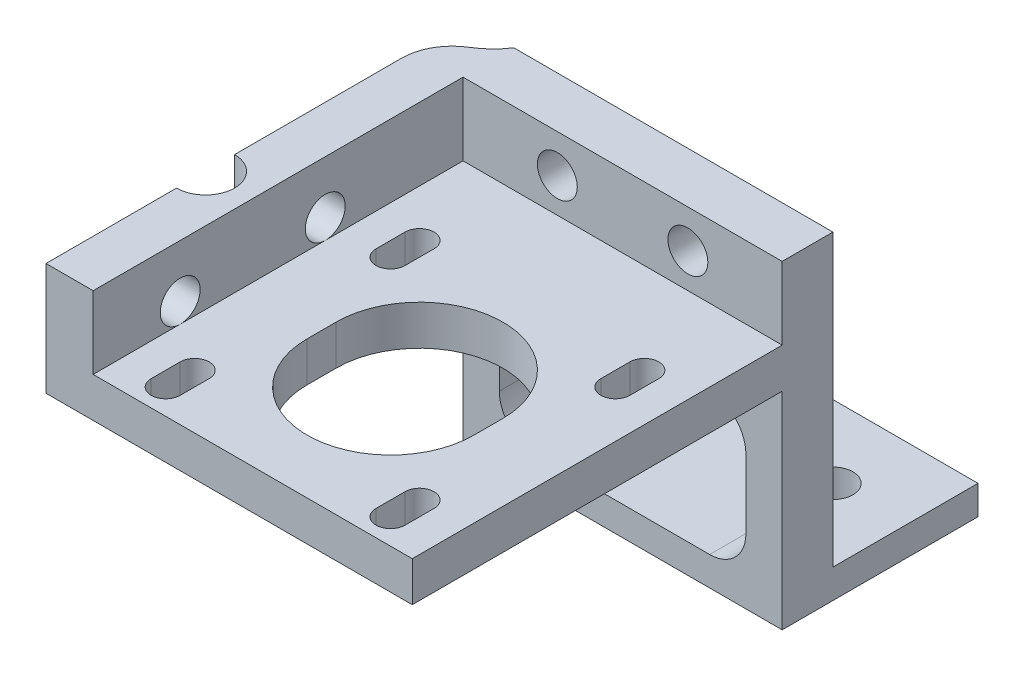
SolidWorks part; units mm, degrees
ref_plane "Front Plane" through (0, 0, 0) normal (0, 0, 1) x (1, 0, 0)
ref_plane "Top Plane" through (0, 0, 0) normal (0, 1, 0) x (1, 0, 0)
ref_plane "Right Plane" through (0, 0, 0) normal (1, 0, 0) x (0, 0, -1)
sketch "Sketch1" plane through (0, 0, 0) normal (1, 0, 0) x (0, 0, -1)
  line L0 (0, 0) -> (0, -62)
  line L1 (0, -62) -> (-5, -62)
  line L3 (-5, 0) -> (0, 0)
  line L4 (-56, 2.5) -> (-65, 2.5)
  line L5 (-65, 2.5) -> (-65, -15.5)
  arc A0 (-5, 0) -> (-56, 2.5) centre (-28.7567, 36.813) cw
  arc A1 (-5, -62) -> (-65, -15.5) centre (-67.324, -80.4584) ccw
  dimension "D3" = 51
  dimension "D5" = 43.813
  dimension "D8" = 65
  dimension "D1" = 5
  dimension "D2" = 62
  dimension "D4" = 2.5
  dimension "D6" = 9
  dimension "D7" = 18
  dimension "D9" = 5
extrude "Boss-Extrude1" add sketch "Sketch1" along normal blind 42 and the other way blind 42
sketch "Sketch2" plane through (0, 0, 0) normal (0, 0, -1) x (-1, 0, 0)
  line L0 (42, -62) -> (-42, -62) construction
  line L1 (-12, -54) -> (12, -54)
  line L2 (-17, -49) -> (-17, -25.5)
  line L3 (-12, -20.5) -> (12, -20.5)
  line L4 (17, -49) -> (17, -25.5)
  line L5 (42, -62) -> (42, 0) construction
  line L6 (42, 0) -> (-42, 0) construction
  line L7 (-42, -62) -> (-42, 0) construction
  line L8 (42, 2.5) -> (-42, 2.5) construction
  line L9 (-42, 0) -> (-27, 0)
  line L10 (-42, 0) -> (-42, 2.5)
  line L11 (-42, 2.5) -> (-27, 2.5)
  line L12 (-27, 0) -> (-27, 2.5)
  line L14 (42, 0) -> (27, 0)
  line L15 (42, 0) -> (42, 2.5)
  line L16 (42, 2.5) -> (27, 2.5)
  line L17 (27, 0) -> (27, 2.5)
  circle A0 centre (-36, -6) radius 2.75
  circle A1 centre (36, -6) radius 2.75
  circle A2 centre (36, -56) radius 2.75
  circle A3 centre (-36, -56) radius 2.75
  arc A4 (12, -20.5) -> (17, -25.5) centre (12, -25.5) cw
  arc A5 (12, -54) -> (17, -49) centre (12, -49) ccw
  arc A6 (-12, -54) -> (-17, -49) centre (-12, -49) cw
  arc A7 (-17, -25.5) -> (-12, -20.5) centre (-12, -25.5) cw
  arc A8 (-42, -8.3208) -> (-42, -53.6792) centre (-65.2788, -31) cw
  arc A9 (42, -8.3208) -> (42, -53.6792) centre (65.2788, -31) ccw
  line M7 (42, 0) -> (-42, 0)
  line M8 (-42, 0) -> (-42, -62)
  line M10 (42, -62) -> (42, 0)
  dimension "D1" = 5.5
  dimension "D2" = 5.5
  dimension "D3" = 5.5
  dimension "D4" = 5.5
  dimension "D9" = 5
  dimension "D18" = 8.3208
  dimension "D20" = 32.5
  dimension "D21" = 8.3208
  dimension "D23" = 32.5
  dimension "D5" = 33.5
  dimension "D6" = 34
  dimension "D7" = 8
  dimension "D8" = 25
  dimension "D10" = 6
  dimension "D11" = 6
  dimension "D12" = 6
  dimension "D13" = 6
  dimension "D14" = 6
  dimension "D15" = 6
  dimension "D16" = 6
  dimension "D17" = 6
  dimension "D19" = 8.3208
  dimension "D22" = 8.3208
  dimension "D24" = 15
  dimension "D25" = 15
extrude "Cut-Extrude1" cut sketch "Sketch2" against normal through all contours A0 | A8 M8 | A7 L2 A6 L1 A5 L4 A4 L3 | A3 | A2 | A1 | L17 L15 L16 M7 | L12 L11 L10 M7 | A9 M10 region at (0, -37.25, 0) region at (34.5, 1.25, 0) region at (-38.2626, -31, 0) region at (-34.5, 1.25, 0) region at (38.2626, -31, 0) region at (36, -6, 0) region at (-36, -6, 0) region at (-36, -56, 0) region at (36, -56, 0)
sketch "Sketch3" plane through (0, -62, 0) normal (0, -1, 0) x (-1, 0, 0)
  line L0 (42, -5) -> (27, -5)
  line L1 (42, -5) -> (-42, -5) construction
  line L2 (27, -5) -> (27, -65)
  line L3 (36.7131, -65) -> (-36.7131, -65) construction
  line L4 (0, -33) -> (0, -37) construction
  line L5 (-27, -65) -> (-27, -5)
  line L6 (-27, -5) -> (-42, -5)
  line L7 (-42, -5) -> (-42, -65)
  line L8 (-42, -65) -> (-27, -65)
  line L9 (42, -65) -> (42, -5)
  line L10 (42, -65) -> (27, -65)
  line L11 (11.5, -33) -> (11.5, -37)
  line L12 (-11.5, -33) -> (-11.5, -37)
  line L13 (15.5, -48.5) -> (15.5, -52.5) construction
  line L14 (17.5, -48.5) -> (17.5, -52.5)
  line L15 (13.5, -48.5) -> (13.5, -52.5)
  line L16 (15.5, -17.5) -> (15.5, -21.5) construction
  line L17 (17.5, -17.5) -> (17.5, -21.5)
  line L18 (13.5, -17.5) -> (13.5, -21.5)
  line L19 (42, 0) -> (-42, 0) construction
  line L20 (0, -65) -> (0, 0) construction
  line L21 (-15.5, -17.5) -> (-15.5, -21.5) construction
  line L22 (-17.5, -17.5) -> (-17.5, -21.5)
  line L23 (-13.5, -17.5) -> (-13.5, -21.5)
  line L24 (-15.5, -48.5) -> (-15.5, -52.5) construction
  line L25 (-17.5, -48.5) -> (-17.5, -52.5)
  line L26 (-13.5, -48.5) -> (-13.5, -52.5)
  circle A0 centre (0, -65) radius 4
  arc A1 (11.5, -33) -> (-11.5, -33) centre (0, -33) ccw
  arc A2 (-11.5, -37) -> (11.5, -37) centre (0, -37) ccw
  arc A3 (17.5, -48.5) -> (13.5, -48.5) centre (15.5, -48.5) ccw
  arc A4 (13.5, -52.5) -> (17.5, -52.5) centre (15.5, -52.5) ccw
  arc A5 (17.5, -17.5) -> (13.5, -17.5) centre (15.5, -17.5) ccw
  arc A6 (13.5, -21.5) -> (17.5, -21.5) centre (15.5, -21.5) ccw
  arc A7 (-17.5, -17.5) -> (-13.5, -17.5) centre (-15.5, -17.5) cw
  arc A8 (-13.5, -21.5) -> (-17.5, -21.5) centre (-15.5, -21.5) cw
  arc A9 (-17.5, -48.5) -> (-13.5, -48.5) centre (-15.5, -48.5) cw
  arc A10 (-13.5, -52.5) -> (-17.5, -52.5) centre (-15.5, -52.5) cw
  point P21 (0, -35)
  point P26 (15.5, -50.5)
  point P33 (15.5, -19.5)
  point P45 (-15.5, -19.5)
  point P52 (-15.5, -50.5)
  dimension "D3" = 8
  dimension "D4" = 11.5
  dimension "D9" = 2
  dimension "D10" = 2
  dimension "D1" = 15
  dimension "D2" = 15
  dimension "D5" = 4
  dimension "D6" = 28
  dimension "D7" = 4
  dimension "D8" = 4
  dimension "D11" = 12.5
  dimension "D12" = 11.5
  dimension "D13" = 17.5
extrude "Cut-Extrude2" cut sketch "Sketch3" against normal through all
sketch "Sketch4" plane through (0, 0, 65) normal (0, 0, 1) x (1, 0, 0)
  line L0 (-27, -62) -> (27, -62) construction
  line L1 (-22, -62) -> (22, -62)
  line L2 (-22, -62) -> (-22, -15.5)
  line L3 (-22, -15.5) -> (22, -15.5)
  line L4 (22, -62) -> (22, -15.5)
  line L5 (4, -15.5) -> (27, -15.5) construction
  line L6 (27, -62) -> (27, -15.5) construction
  line L7 (-27, -15.5) -> (-27, -62) construction
  dimension "D1" = 46.5
  dimension "D2" = 5
  dimension "D3" = 5
extrude "Cut-Extrude3" cut sketch "Sketch4" against normal blind 60
sketch "Sketch5" plane through (0, 0, 0) normal (0, 1, 0) x (1, 0, 0)
  line L0 (-27, -56) -> (27, -56) construction
  line L1 (-22, -56) -> (22, -56)
  line L2 (-22, -56) -> (-22, -5)
  line L3 (-22, -5) -> (22, -5)
  line L4 (22, -56) -> (22, -5)
  line L5 (-27, -5) -> (27, -5) construction
  line L6 (-27, -5) -> (-27, -56) construction
  line L7 (27, -56) -> (27, -5) construction
  dimension "D1" = 5
  dimension "D2" = 5
extrude "Cut-Extrude4" cut sketch "Sketch5" against normal blind 10 and the other way blind 10
sketch "Sketch6" plane through (0, 0, 65) normal (0, 0, 1) x (1, 0, 0)
  line L0 (-27, 2.5) -> (-4, 2.5) construction
  line L1 (4, 2.5) -> (27, 2.5) construction
  circle A0 centre (-10, -5.5) radius 2.75
  circle A1 centre (10, -5.5) radius 2.75
  dimension "D1" = 5.5
  dimension "D2" = 5.5
  dimension "D3" = 10
  dimension "D4" = 10
  dimension "D5" = 8
  dimension "D6" = 8
extrude "Cut-Extrude5" cut sketch "Sketch6" against normal blind 4.6
sketch "Sketch7" plane through (0, 0, 5) normal (0, 0, 1) x (1, 0, 0)
  line L1 (27, 0) -> (42, 0)
  line L2 (27, 0) -> (27, -62)
  line L3 (27, -62) -> (42, -62)
  line L4 (42, 0) -> (42, -62)
  line L5 (-27, -62) -> (-42, -62)
  line L6 (-27, -62) -> (-27, 0)
  line L7 (-27, 0) -> (-42, 0)
  line L8 (-42, -62) -> (-42, 0)
extrude "Cut-Extrude6" cut sketch "Sketch7" against normal blind 63
sketch "Sketch8" plane through (0, 0, 0) normal (0, 0, -1) x (-1, 0, 0)
  line L0 (27, 0) -> (27, -62) construction
  line L1 (-27, -62) -> (27, -62)
  line L2 (-27, -62) -> (-27, -40)
  line L3 (-27, -40) -> (27, -40)
  line L4 (27, -62) -> (27, -40)
  dimension "D1" = 22
extrude "Cut-Extrude7" cut sketch "Sketch8" against normal blind 63
sketch "Sketch9" plane through (0, -40, 0) normal (0, -1, 0) x (1, 0, 0)
  line L1 (-27, 5) -> (27, 5)
  line L2 (-27, 5) -> (-27, -22)
  line L3 (-27, -22) -> (27, -22)
  line L4 (27, 5) -> (27, -22)
  dimension "D1" = 54
  dimension "D2" = 27
extrude "Boss-Extrude2" add sketch "Sketch9" along normal blind 4
fillet "Fillet1" radius 5 2 edges at (17, -40, 2.5) (-17, -40, 2.5)
sketch "Sketch12" plane through (0, -40, 0) normal (0, -1, 0) x (1, 0, 0)
  line L1 (-27, 16.4505) -> (-22, 16.4505)
  line L2 (-27, 16.4505) -> (-27, 5)
  line L3 (-27, 5) -> (-22, 5)
  line L4 (-22, 16.4505) -> (-22, 5)
  line L5 (22, 16.4505) -> (27, 16.4505)
  line L6 (22, 16.4505) -> (22, 5)
  line L7 (22, 5) -> (27, 5)
  line L8 (27, 16.4505) -> (27, 5)
extrude "Boss-Extrude4" add sketch "Sketch12" along normal blind 4
sketch "Sketch13" plane through (27, 0, 0) normal (1, 0, 0) x (0, 0, -1)
  circle A0 centre (-67.324, -80.4584) radius 65
extrude "Cut-Extrude8" cut sketch "Sketch13" against normal blind 113
sketch "Sketch14" plane through (0, -44, 0) normal (0, -1, 0) x (1, 0, 0)
  line L0 (-27, -22) -> (27, -22) construction
  line L3 (-22, 5) -> (-22, 13.5116) construction
  line L5 (22, 13.5116) -> (22, 5) construction
  circle A0 centre (12, -12) radius 2.75
  circle A1 centre (-12, -12) radius 2.75
  dimension "D1" = 5.5
  dimension "D4" = 10
  dimension "D2" = 10
  dimension "D3" = 10
extrude "Cut-Extrude9" cut sketch "Sketch14" against normal blind 15
sketch "Sketch15" plane through (0, 0, 5) normal (0, 0, 1) x (1, 0, 0)
  line L0 (-22, 0) -> (22, 0) construction
  line L1 (27, -7) -> (27, 2.5) construction
  line L2 (-27, 2.5) -> (-27, -7) construction
  circle A0 centre (9, -5.25) radius 2.75
  circle A1 centre (-9, -5.25) radius 2.75
  dimension "D1" = 5.5
  dimension "D4" = 18
  dimension "D2" = 5.25
  dimension "D3" = 18
extrude "Cut-Extrude10" cut sketch "Sketch15" against normal blind 15
sketch "Sketch16" plane through (0, 0, 65) normal (0, 0, 1) x (1, 0, 0)
  line L1 (-27, 2.5) -> (-22, 2.5)
  line L2 (-27, 2.5) -> (-27, -44)
  line L3 (-27, -44) -> (-22, -44)
  line L4 (-22, 2.5) -> (-22, -44)
  line L5 (27, 2.5) -> (22, 2.5)
  line L6 (27, 2.5) -> (27, -44)
  line L7 (27, -44) -> (22, -44)
  line L8 (22, 2.5) -> (22, -44)
extrude "Cut-Extrude11" cut sketch "Sketch16" against normal blind 90
sketch "Sketch17" plane through (-22, 0, 0) normal (-1, 0, 0) x (0, 0, 1)
  line L0 (5, -15.5) -> (65, -15.5) construction
  line L1 (65, 2.5) -> (56, 2.5)
  line L2 (65, 2.5) -> (65, -15.5)
  line L3 (65, -15.5) -> (56, -15.5)
  line L4 (56, 2.5) -> (56, -15.5)
  dimension "D1" = 9
extrude "Cut-Extrude12" cut sketch "Sketch17" against normal blind 90
sketch "Sketch18" plane through (-22, 0, 0) normal (-1, 0, 0) x (0, 0, 1)
  line L1 (56, -15.5) -> (0, -15.5)
  line L2 (56, -15.5) -> (56, 0)
  line L3 (56, 0) -> (0, 0)
  line L4 (0, -15.5) -> (0, 0)
  circle A0 centre (24, -7.25) radius 2.75
  circle A1 centre (44, -7.25) radius 2.75
  dimension "D1" = 5.5
  dimension "D2" = 20
  dimension "D3" = 12
  dimension "D4" = 7.25
extrude "Boss-Extrude5" add sketch "Sketch18" along normal blind 6.5
sketch "Sketch19" plane through (0, -15.5, 0) normal (0, -1, 0) x (1, 0, 0)
  line L0 (-28.5, 0) -> (-28.5, 56) construction
  circle A0 centre (-28.5, 34) radius 4
  dimension "D2" = 8
  dimension "D1" = 22
extrude "Cut-Extrude13" cut sketch "Sketch19" against normal blind 36
fillet "Fillet2" radius 7 1 edges at (-28.5, -7.75, 0)
sketch "Sketch20" plane through (0, 0, 0) normal (0, 0, -1) x (-1, 0, 0)
  line L0 (-22, 0) -> (-22, -40)
  line L1 (-22, -40) -> (21.5, -40)
  line L3 (-22, 0) -> (21.5, 0)
  line L4 (21.5, 0) -> (20.9974, -0.0066)
  line L5 (-17, -35) -> (-17, -25.5)
  line L6 (12, -20.5) -> (-12, -20.5)
  line L7 (17, -25.5) -> (17, -35)
  circle A0 centre (-9, -5.25) radius 2.75
  circle A1 centre (9, -5.25) radius 2.75
  arc A2 (-17, -35) -> (-12, -40) centre (-12, -35) ccw
  arc A3 (-12, -20.5) -> (-17, -25.5) centre (-12, -25.5) ccw
  arc A8 (17, -25.5) -> (12, -20.5) centre (12, -25.5) ccw
  arc A9 (12, -40) -> (17, -35) centre (12, -35) ccw
  line M1 (12, -40) -> (21.5, -40)
  line M2 (21.5, -40) -> (21.5, 0)
  line M3 (21.5, 0) -> (-22, 0)
  line M4 (-22, 0) -> (-22, -40)
  line M5 (-22, -40) -> (-12, -40)
  arc M6 (-12, -40) -> (-17, -35) centre (-12, -35) cw
  line M7 (-17, -35) -> (-17, -25.5)
  arc M8 (-17, -25.5) -> (-12, -20.5) centre (-12, -25.5) cw
  line M9 (-12, -20.5) -> (12, -20.5)
  arc M10 (12, -20.5) -> (17, -25.5) centre (12, -25.5) cw
  line M11 (17, -25.5) -> (17, -35)
  arc M12 (17, -35) -> (12, -40) centre (12, -35) cw
  circle M13 centre (9, -5.25) radius 2.75
  circle M14 centre (-9, -5.25) radius 2.75
extrude "Boss-Extrude6" add sketch "Sketch20" along normal blind 2 contours M12 M1 M2 M3 M4 M5 M6 M7 M8 M9 M10 M11 M13 M14 region at (0.4139, -14.4099, 0)
sketch "Sketch21" plane through (-21.5, 0, 0) normal (-1, 0, 0) x (0, 0, 1)
  line L1 (-2, 0) -> (0.0179, 0)
  line L2 (-2, 0) -> (-2, -40)
  line L3 (-2, -40) -> (0.0179, -40)
  line L4 (0.0179, 0) -> (0.0179, -40)
extrude "Boss-Extrude7" add sketch "Sketch21" along normal up to surface (0.5 mm away) up to face at (-22, -33.1667, -5.6607)
fillet "Fillet4" radius 10 1 edges at (-22, -7.75, 0.0179)
